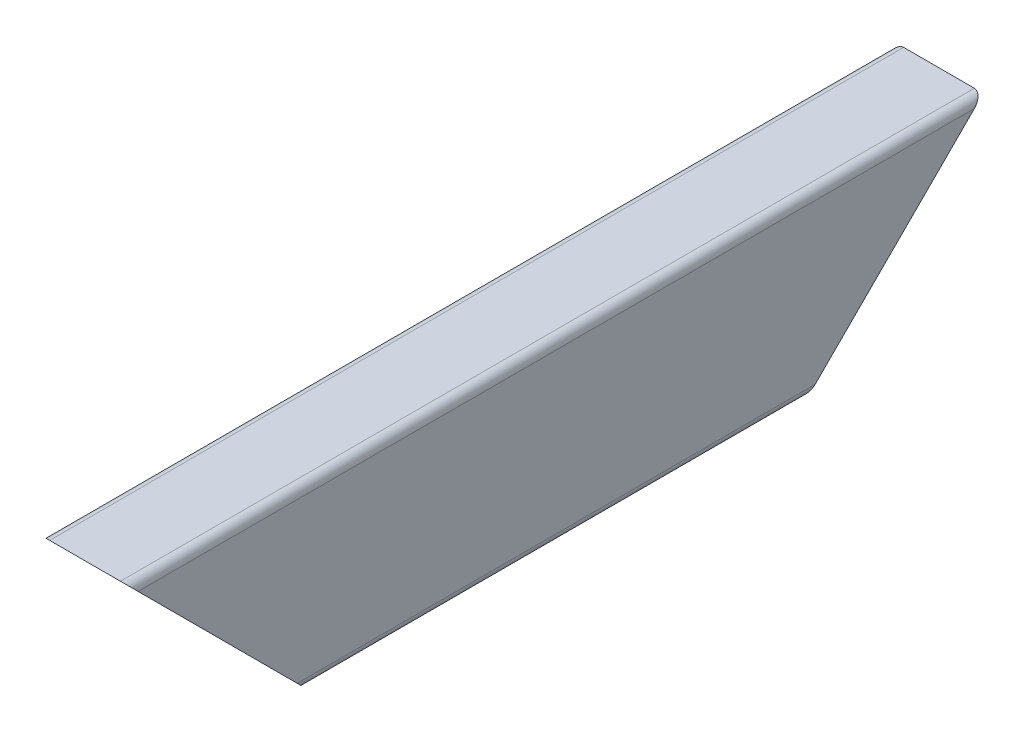
SolidWorks part; units mm, degrees
material "6061-T6 (SS)"
ref_plane "Front" through (0, 0, 0) normal (0, 0, 1) x (1, 0, 0)
ref_plane "Top" through (0, 0, 0) normal (0, 1, 0) x (1, 0, 0)
ref_plane "Right" through (0, 0, 0) normal (1, 0, 0) x (0, 0, -1)
sketch "Sketch3" plane through (0, 0, 0) normal (1, 0, 0) x (0, 0, -1)
  line L0 (-50.8, -25.4) -> (-194.4841, -25.4)
  line L1 (-194.4841, -25.4) -> (-245.2841, 25.4)
  line L2 (-245.2841, 25.4) -> (0, 25.4)
  line L3 (0, 25.4) -> (-50.8, -25.4)
  point P8 (-25.4, 0)
  dimension "D1" = 50.8
  dimension "D2" = 101.6
  dimension "D3" = 45
sketch "Sketch1" plane through (0, 0, 0) normal (0, 0, 1) x (1, 0, 0)
  line L1 (-10.16, -25.4) -> (10.16, -25.4)
  line L2 (-12.7, -22.86) -> (-12.7, 22.86)
  line L3 (-10.16, 25.4) -> (10.16, 25.4)
  line L4 (12.7, -22.86) -> (12.7, 22.86)
  line L5 (-12.7, -25.4) -> (12.7, 25.4) construction
  line L6 (-12.7, 25.4) -> (12.7, -25.4) construction
  arc A0 (-10.16, -25.4) -> (-12.7, -22.86) centre (-10.16, -22.86) cw
  arc A1 (10.16, -25.4) -> (12.7, -22.86) centre (10.16, -22.86) ccw
  arc A2 (10.16, 25.4) -> (12.7, 22.86) centre (10.16, 22.86) cw
  arc A3 (-12.7, 22.86) -> (-10.16, 25.4) centre (-10.16, 22.86) cw
  point P0 (0, 0)
  dimension "D3" = 2.54
  dimension "D1" = 25.4
  dimension "D2" = 50.8
extrude "Extrude-Thin1" add sketch "Sketch1" along normal up to vertex (245.2841 mm away) thin up to point (0, 25.4, 245.2841) thin type one direction reverse wall 1.5875
sketch "Sketch2" plane through (12.7, 0, 0) normal (1, 0, 0) x (0, 0, -1)
  line L0 (-245.2841, 25.4) -> (-194.4841, -25.4)
  line L1 (-245.2841, -25.4) -> (0, -25.4) construction
  line L2 (-194.4841, -25.4) -> (-245.2841, -25.4)
  line L3 (-245.2841, -25.4) -> (-245.2841, 25.4)
  line L4 (0, 25.4) -> (-50.8, -25.4)
  line L5 (-50.8, -25.4) -> (0, -25.4)
  line L6 (0, -25.4) -> (0, 25.4)
  line L7 (0, 25.4) -> (-50.8, -25.4) construction
  line L8 (-194.4841, -25.4) -> (-245.2841, 25.4) construction
extrude "Cut-Extrude1" cut sketch "Sketch2" against normal through all
